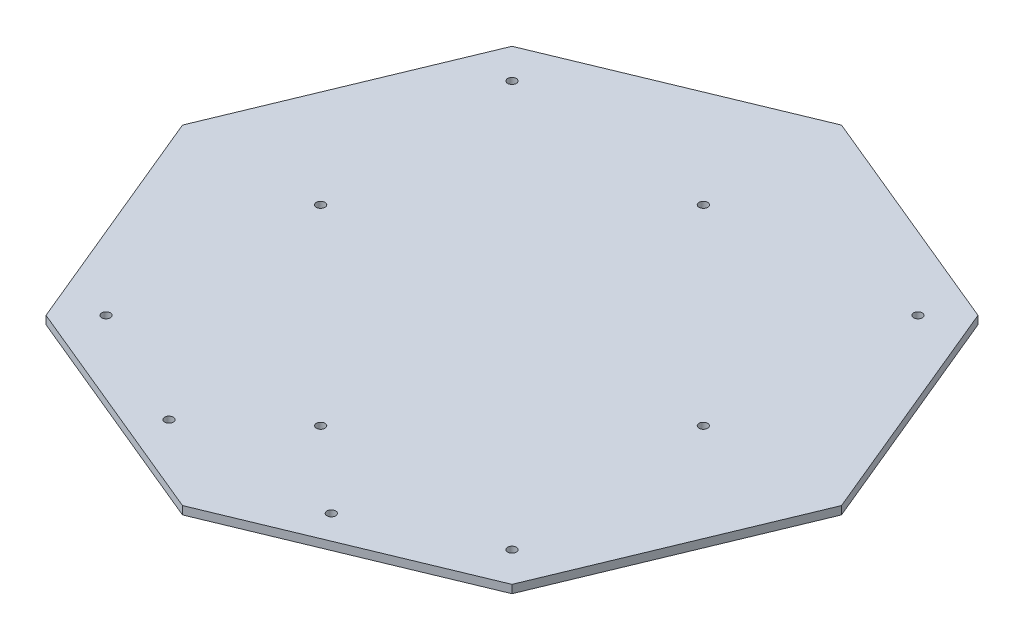
SolidWorks part; units mm, degrees
ref_plane "Front Plane" through (0, 0, 0) normal (0, 0, 1) x (1, 0, 0)
ref_plane "Top Plane" through (0, 0, 0) normal (0, 1, 0) x (1, 0, 0)
ref_plane "Right Plane" through (0, 0, 0) normal (1, 0, 0) x (0, 0, -1)
sketch "Sketch1" plane through (0, 0, 0) normal (0, 1, 0) x (1, 0, 0)
  line L0 (0, -121.7691) -> (86.1038, -86.1038)
  line L7 (0, 121.7691) -> (-86.1038, 86.1038)
  line L8 (-86.1038, 86.1038) -> (-121.7691, 0)
  line L9 (-121.7691, 0) -> (-86.1038, -86.1038)
  line L10 (-86.1038, -86.1038) -> (0, -121.7691)
  line L11 (86.1038, -86.1038) -> (121.7691, 0)
  line L12 (121.7691, 0) -> (86.1038, 86.1038)
  line L13 (86.1038, 86.1038) -> (0, 121.7691)
  circle A0 centre (0, 0) radius 112.5 construction
  dimension "D1" = 225
extrude "Boss-Extrude2" add sketch "Sketch1" along normal blind 3
sketch "Sketch3" plane through (0, 3, 0) normal (0, 1, 0) x (1, 0, 0)
  line L0 (-121.7691, 0) -> (121.7691, 0) construction
  line L1 (0, 121.7691) -> (0, -121.7691) construction
  line L2 (-75, -75) -> (0, 0) construction
  circle A0 centre (-75, -75) radius 1.6
  circle A1 centre (75, -75) radius 1.6
  circle A2 centre (75, 75) radius 1.6
  circle A3 centre (-75, 75) radius 1.6
  circle A4 centre (-70.7107, 0) radius 1.6
  circle A5 centre (0, 70.7107) radius 1.6
  circle A6 centre (70.7107, 0) radius 1.6
  circle A7 centre (0, -70.7107) radius 1.6
  point P28 (0, 0)
  dimension "D1" = 3.2
  dimension "D4" = 3.2
  dimension "D2" = 150
  dimension "D3" = 150
  dimension "D6" = 100
  dimension "D5" = 4
extrude "Cut-Extrude3" cut sketch "Sketch3" against normal through all both and the other way through all
sketch "Sketch4" plane through (0, 3, 0) normal (0, 1, 0) x (1, 0, 0)
  line L0 (0, -121.7691) -> (0, -96.7691) construction
  circle A0 centre (-30, -96.7691) radius 1.6
  circle A1 centre (30, -96.7691) radius 1.6
  point P6 (0, 0)
  dimension "D1" = 3.2
  dimension "D2" = 60
  dimension "D3" = 25
extrude "Cut-Extrude4" cut sketch "Sketch4" against normal through all both and the other way through all
